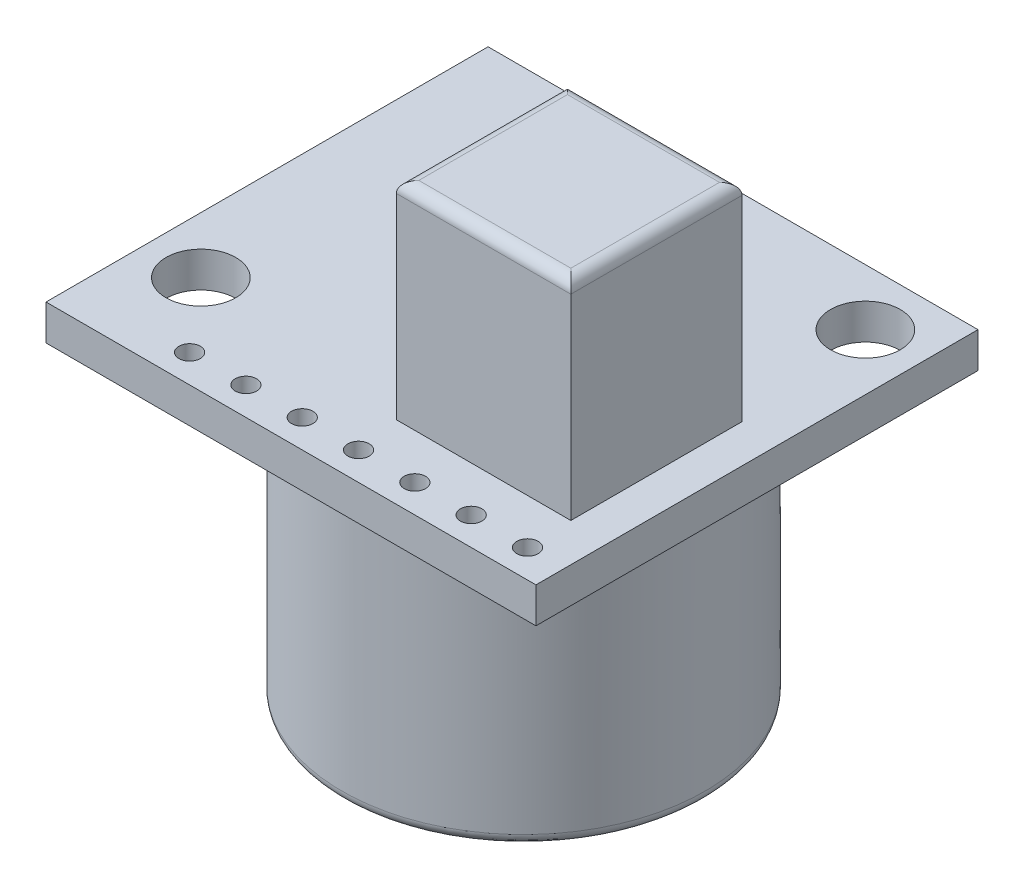
SolidWorks part; units mm, degrees
ref_plane "Front Plane" through (0, 0, 0) normal (0, 0, 1) x (1, 0, 0)
ref_plane "Top Plane" through (0, 0, 0) normal (0, 1, 0) x (1, 0, 0)
ref_plane "Right Plane" through (0, 0, 0) normal (1, 0, 0) x (0, 0, -1)
sketch "Sketch1" plane through (0, 0, 0) normal (0, 1, 0) x (1, 0, 0)
  line L1 (-11.049, 9.9695) -> (11.049, 9.9695)
  line L2 (-11.049, 9.9695) -> (-11.049, -9.9695)
  line L3 (-11.049, -9.9695) -> (11.049, -9.9695)
  line L4 (11.049, 9.9695) -> (11.049, -9.9695)
  circle A0 centre (8.509, 7.4295) radius 1.5748
  circle A1 centre (-8.509, -5.5245) radius 1.5748
  circle A2 centre (9.398, -8.6995) radius 0.4826
  circle A3 centre (6.858, -8.6995) radius 0.4826
  circle A4 centre (4.318, -8.6995) radius 0.4826
  circle A5 centre (1.778, -8.6995) radius 0.4826
  circle A6 centre (-0.762, -8.6995) radius 0.4826
  circle A7 centre (-3.302, -8.6995) radius 0.4826
  circle A8 centre (-5.842, -8.6995) radius 0.4826
  point P9 (0, 0)
  dimension "D3" = 2.54
  dimension "D7" = 1.651
  dimension "D1" = 19.939
  dimension "D2" = 22.098
  dimension "D4" = 2.54
  dimension "D5" = 17.018
  dimension "D6" = 15.494
  dimension "D8" = 18.669
  dimension "D9" = 7
extrude "Boss-Extrude1" add sketch "Sketch1" along normal blind 1.6002
sketch "Sketch2" plane through (0, 1.6002, 0) normal (0, 1, 0) x (1, 0, 0)
  line L0 (11.049, 9.9695) -> (-11.049, 9.9695) construction
  line L1 (1.4478, 1.0541) -> (9.3218, 1.0541)
  line L2 (1.4478, 1.0541) -> (1.4478, -6.6675)
  line L3 (1.4478, -6.6675) -> (9.3218, -6.6675)
  line L4 (9.3218, 1.0541) -> (9.3218, -6.6675)
  dimension "D1" = 7.7216
  dimension "D2" = 12.4968
  dimension "D3" = 8.9154
  dimension "D4" = 7.874
extrude "Boss-Extrude2" add sketch "Sketch2" along normal blind 9.3472
sketch "Sketch3" plane through (1.4478, 0, 0) normal (-1, 0, 0) x (0, 0, 1)
  line L1 (0.5915, 9.4713) -> (5.2816, 9.4713)
  line L2 (0.5915, 9.4713) -> (0.5915, 6.1544)
  line L3 (0.5915, 6.1544) -> (5.2816, 6.1544)
  line L4 (5.2816, 9.4713) -> (5.2816, 6.1544)
  line L5 (-0.2113, 5.6474) -> (0.9507, 5.6474)
  line L6 (-0.2113, 5.6474) -> (-0.2113, 4.9924)
  line L7 (-0.2113, 4.9924) -> (0.9507, 4.9924)
  line L8 (0.9507, 5.6474) -> (0.9507, 4.9924)
  line L9 (4.669, 5.6474) -> (5.7253, 5.6474)
  line L10 (4.669, 5.6474) -> (4.669, 4.9924)
  line L11 (4.669, 4.9924) -> (5.7253, 4.9924)
  line L12 (5.7253, 5.6474) -> (5.7253, 4.9924)
sketch "Sketch4" plane through (9.3218, 0, 0) normal (1, 0, 0) x (0, 0, -1)
  line L1 (-5.2816, 9.4713) -> (-0.5915, 9.4713)
  line L2 (-5.2816, 9.4713) -> (-5.2816, 6.1544)
  line L3 (-5.2816, 6.1544) -> (-0.5915, 6.1544)
  line L4 (-0.5915, 9.4713) -> (-0.5915, 6.1544)
  line L5 (-5.7253, 5.6474) -> (-4.669, 5.6474)
  line L6 (-5.7253, 5.6474) -> (-5.7253, 4.9924)
  line L7 (-5.7253, 4.9924) -> (-4.669, 4.9924)
  line L8 (-4.669, 5.6474) -> (-4.669, 4.9924)
  line L9 (-0.9507, 5.6474) -> (0.2113, 5.6474)
  line L10 (-0.9507, 5.6474) -> (-0.9507, 4.9924)
  line L11 (-0.9507, 4.9924) -> (0.2113, 4.9924)
  line L12 (0.2113, 5.6474) -> (0.2113, 4.9924)
sketch "Sketch5" plane through (0, 10.9474, 0) normal (0, 1, 0) x (1, 0, 0)
  circle A0 centre (5.5484, -2.6184) radius 3.2763
sketch "Sketch7" plane through (0, 0, 0) normal (0, -1, 0) x (1, 0, 0)
  line L0 (-11.049, 9.9695) -> (11.049, 9.9695) construction
  line L1 (11.049, 9.9695) -> (11.049, -9.9695) construction
  circle A0 centre (0, -0.5207) radius 8.1915
  dimension "D1" = 10.4902
  dimension "D2" = 11.049
extrude "Boss-Extrude6" add sketch "Sketch7" along normal blind 13.6398
sketch "Sketch8" plane through (0, 0, 0) normal (0, -1, 0) x (1, 0, 0)
  line L0 (-11.049, -9.9695) -> (-11.049, 9.9695) construction
  line L1 (-10.541, -7.9375) -> (-5.969, -7.9375)
  line L2 (-10.541, -7.9375) -> (-10.541, -1.3335)
  line L3 (-10.541, -1.3335) -> (-5.969, -1.3335)
  line L4 (-5.969, -7.9375) -> (-5.969, -1.3335)
  line L5 (11.049, -9.9695) -> (-11.049, -9.9695) construction
  dimension "D1" = 6.604
  dimension "D2" = 4.572
  dimension "D3" = 0.508
  dimension "D4" = 2.032
extrude "Boss-Extrude7" add sketch "Sketch8" along normal blind 2.032
fillet "Fillet2" radius 0.508 1 edges at (0, -13.6398, -8.7122)
fillet "Fillet3" radius 0.508 4 edges at (5.3848, 10.9474, -1.0541) (1.4478, 10.9474, 2.8067) (5.3848, 10.9474, 6.6675) (9.3218, 10.9474, 2.8067)
